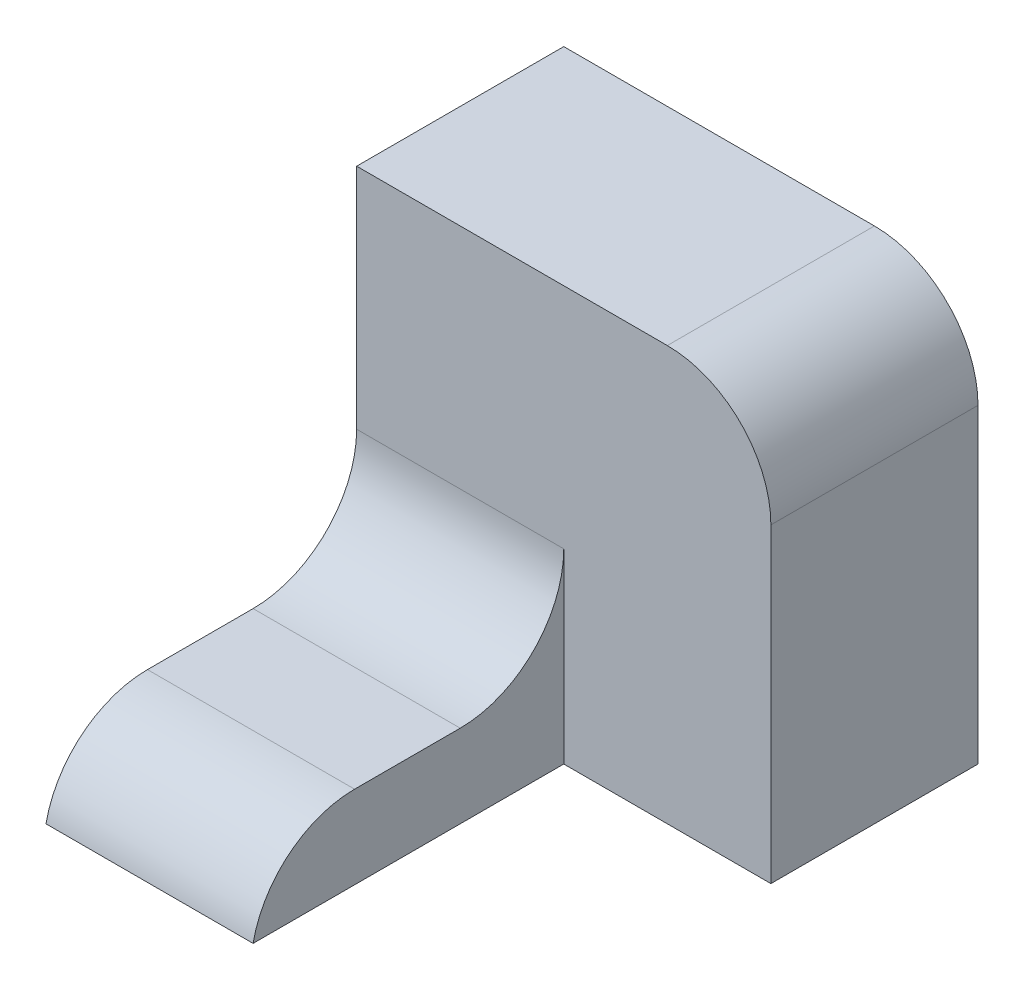
SolidWorks part; units mm, degrees
ref_plane "Front Plane" through (0, 0, 0) normal (0, 0, 1) x (1, 0, 0)
ref_plane "Top Plane" through (0, 0, 0) normal (0, 1, 0) x (1, 0, 0)
ref_plane "Right Plane" through (0, 0, 0) normal (1, 0, 0) x (0, 0, -1)
sketch "Sketch1" plane through (0, 0, 0) normal (0, 0, 1) x (1, 0, 0)
  line L1 (-30, -8) -> (-10, -8)
  line L2 (-10, -8) -> (-10, 0)
  line L3 (-10, 0) -> (-30, 0)
  line L4 (-30, 0) -> (-30, -8)
  dimension "D1" = 20
  dimension "Width" = 8
extrude "Boss-Extrude1" add sketch "Sketch1" along normal blind 30
sketch "Sketch2" plane through (0, 0, 0) normal (0, 0, 1) x (1, 0, 0)
  line L1 (-30, -8) -> (10, -8)
  line L2 (10, -8) -> (10, 32)
  line L3 (10, 32) -> (-30, 32)
  line L4 (-30, 32) -> (-30, -8)
  dimension "D1" = 40
  dimension "Width" = 40
extrude "Boss-Extrude2" add sketch "Sketch2" against normal blind 20
fillet "Fillet1" radius 10 3 edges at (-20, 0, 0) (10, 32, -10) (-20, 0, 30)
